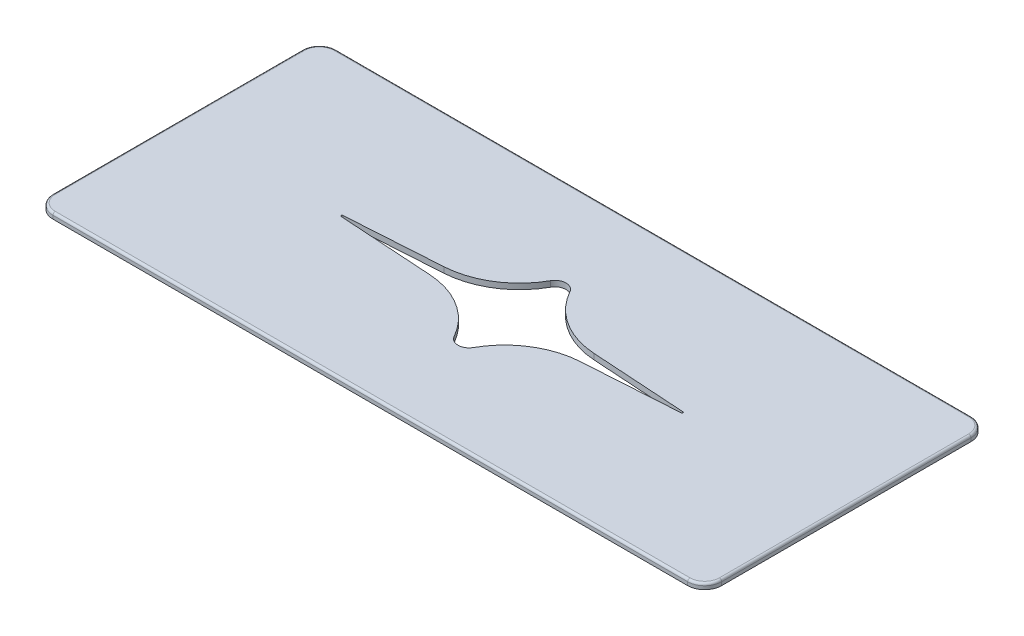
SolidWorks part; units mm, degrees
material "201 Annealed Stainless Steel (SS)"
ref_plane "Front Plane" through (0, 0, 0) normal (0, 0, 1) x (1, 0, 0)
ref_plane "Top Plane" through (0, 0, 0) normal (0, 1, 0) x (1, 0, 0)
ref_plane "Right Plane" through (0, 0, 0) normal (1, 0, 0) x (0, 0, -1)
sketch "Sketch1" plane through (0, 0, 0) normal (0, 1, 0) x (1, 0, 0)
  line L1 (-147.5, 62.5) -> (147.5, 62.5)
  line L2 (-147.5, 62.5) -> (-147.5, -62.5)
  line L3 (-147.5, -62.5) -> (147.5, -62.5)
  line L4 (147.5, 62.5) -> (147.5, -62.5)
  line L5 (-147.5, 62.5) -> (147.5, -62.5) construction
  line L6 (-147.5, -62.5) -> (147.5, 62.5) construction
  point P0 (0, 0)
  dimension "D1" = 295
  dimension "D2" = 125
extrude "Boss-Extrude1" add sketch "Sketch1" along normal blind 2.5
fillet "Fillet1" radius 7.5 4 edges at (147.5, 1.25, 62.5) (-147.5, 1.25, 62.5) (147.5, 1.25, -62.5) (-147.5, 1.25, -62.5)
fillet "Fillet2" radius 1 8 edges at (145.3033, 2.5, -60.3033) (147.5, 2.5, 0) (145.3033, 2.5, 60.3033) (0, 2.5, 62.5) (-145.3033, 2.5, 60.3033) (-147.5, 2.5, 0) (-145.3033, 2.5, -60.3033) (0, 2.5, -62.5)
sketch "Sketch4" plane through (0, 2.5, 0) normal (0, 1, 0) x (1, 0, 0)
  line L0 (-75.0254, 0.3951) -> (-33.074, 3.09)
  line L1 (-75, 0) -> (75, 0) construction
  line L2 (-75, 1.25) -> (75, 1.25) construction
  line L3 (-75, -1.25) -> (75, -1.25) construction
  line L4 (0, 34.3443) -> (0, 0) construction
  line L5 (75.0254, 0.3951) -> (33.074, 3.09)
  line L6 (-23.8422, 0) -> (49433.0468, 0) construction
  line L7 (-75.0254, -0.3951) -> (-33.074, -3.09)
  line L8 (75.0254, -0.3951) -> (33.074, -3.09)
  arc A0 (-75, 1.25) -> (-75, -1.25) centre (-75, 0) ccw construction
  arc A1 (75, -1.25) -> (75, 1.25) centre (75, 0) ccw construction
  circle A2 centre (-75, 0) radius 0.3959
  arc A3 (-33.074, 3.09) -> (0, 34.3443) centre (-35.3573, 38.6332) ccw
  circle A4 centre (75, 0) radius 0.3959
  arc A5 (33.074, 3.09) -> (0, 34.3443) centre (35.3573, 38.6332) cw
  arc A6 (-33.074, -3.09) -> (0, -34.3443) centre (-35.3573, -38.6332) cw
  arc A7 (33.074, -3.09) -> (0, -34.3443) centre (35.3573, -38.6332) ccw
  arc A8 (-4.2367, 21.3115) -> (4.2367, 21.3115) centre (0, 18.9533) cw
  arc A9 (-4.2367, -21.3115) -> (4.2367, -21.3115) centre (0, -18.9533) ccw
  point P4 (0, 0)
  point P6 (0, 0)
  dimension "D1" = 150
  dimension "D2" = 2.5
extrude "Cut-Extrude4" cut sketch "Sketch4" against normal blind 10 contours A6 A9 A7 L8 A4 L5 A5 A8 A3 L0 A2 L7 | A2 | A4 region at (0, 2.5, 0)
sketch "Sketch3" plane through (0, 2.5, 0) normal (0, 1, 0) x (1, 0, 0)
  line L1 (-110, -25) -> (110, -25) construction
  line L2 (-110, -25) -> (-110, 25) construction
  line L3 (-110, 25) -> (110, 25) construction
  line L4 (110, -25) -> (110, 25) construction
  text T0 "LUNAR" font "Century Gothic" height 50
  point P4 (-110, 0)
  point P6 (0, 25)
  dimension "D1" = 220
  dimension "D2" = 50
extrude "Cut-Extrude3" [suppressed] cut sketch "Sketch3" against normal blind 0.5
